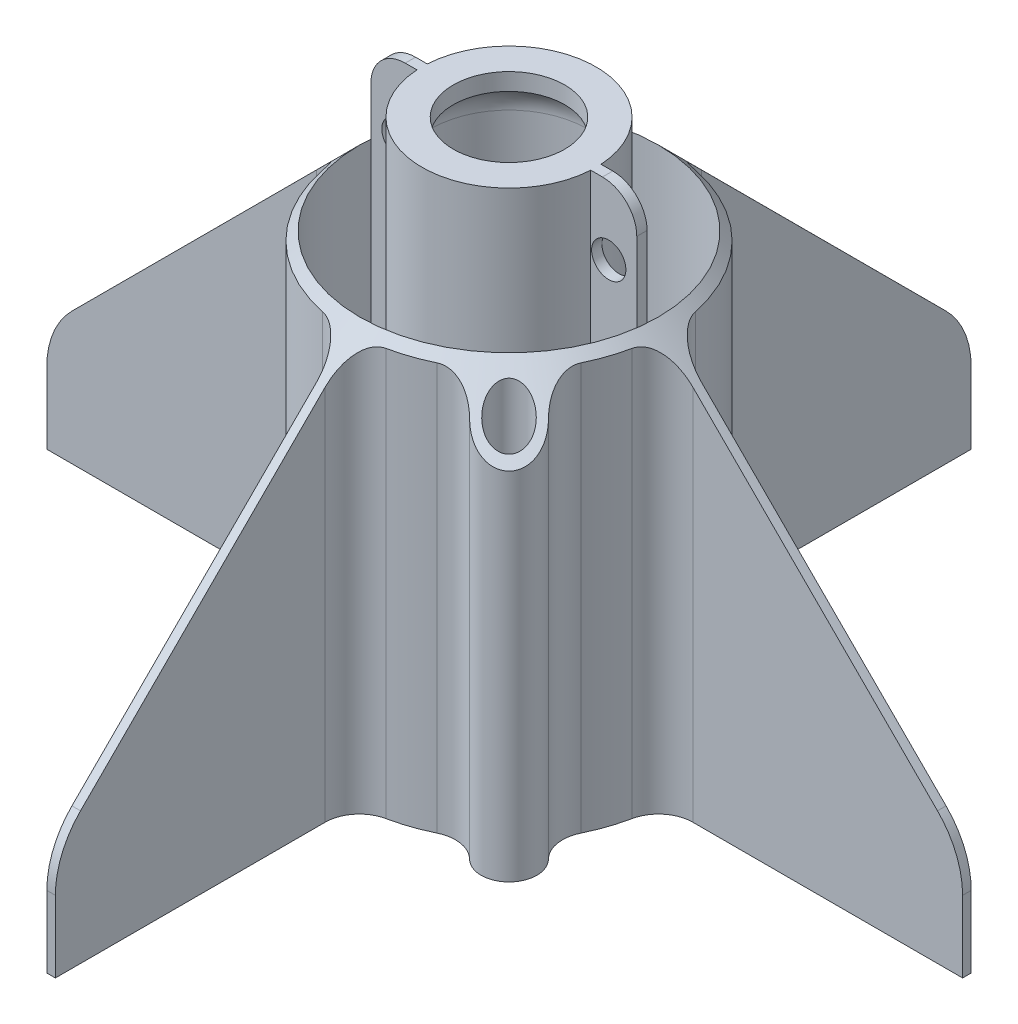
SolidWorks part; units mm, degrees
ref_plane "Front Plane" through (0, 0, 0) normal (0, 0, 1) x (1, 0, 0)
ref_plane "Top Plane" through (0, 0, 0) normal (0, 1, 0) x (1, 0, 0)
ref_plane "Right Plane" through (0, 0, 0) normal (1, 0, 0) x (0, 0, -1)
sketch "Sketch1" plane through (0, 0, 0) normal (0, 0, 1) x (1, 0, 0)
  line L0 (6.5, 60) -> (10.15, 60)
  line L1 (10.15, 60) -> (10.15, 1.5)
  line L2 (10.15, 1.5) -> (17.4, 1.5)
  line L3 (17.4, 1.5) -> (17.4, 50)
  line L4 (17.4, 50) -> (18.4, 50)
  line L5 (18.4, 50) -> (18.4, 0)
  line L6 (18.4, 0) -> (9.15, 0)
  line L7 (9.15, 0) -> (9.15, 58)
  line L8 (9.15, 58) -> (6.5, 58)
  line L9 (6.5, 58) -> (6.5, 60)
  line L10 (0, -33) -> (0, 33) construction
  line L11 (-6.5, 58) -> (-6.5, 60) construction
  line L12 (-9.15, 58) -> (-6.5, 58) construction
  line L13 (-9.15, 0) -> (-9.15, 58) construction
  line L14 (-18.4, 0) -> (-9.15, 0) construction
  line L15 (-18.4, 50) -> (-18.4, 0) construction
  line L16 (-17.4, 50) -> (-18.4, 50) construction
  line L17 (-17.4, 1.5) -> (-17.4, 50) construction
  line L18 (-10.15, 1.5) -> (-17.4, 1.5) construction
  line L19 (-10.15, 60) -> (-10.15, 1.5) construction
  line L20 (-6.5, 60) -> (-10.15, 60) construction
  line L21 (0, 0) -> (0, 125) construction
  dimension "D1" = 2
  dimension "D2" = 1.5
  dimension "D3" = 50
  dimension "D4" = 60
  dimension "D5" = 18.3
  dimension "D6" = 20.3
  dimension "D7" = 13
  dimension "D8" = 34.8
  dimension "D9" = 36.8
revolve "Revolve2" add sketch "Sketch1" angle 360 about L21
sketch "Sketch3" plane through (0, 0, 0) normal (1, 0, 0) x (0, 0, -1)
  line L0 (-18.4, 50) -> (-18.4, 0) construction
  line L1 (-17.9, 50) -> (-17.9, 0) construction
  line L2 (17.4, 50) -> (-17.4, 50) construction
  line L3 (-18.4, 50) -> (-53.4, 50)
  line L4 (18.4, 50) -> (-18.4, 50) construction
  line L5 (-53.4, 50) -> (-53.4, 0)
  line L6 (-53.4, 0) -> (-17.9, 0)
  line L7 (-18.4, 50) -> (-17.9, 50)
  line L8 (-17.9, 50) -> (-17.9, 0)
  dimension "D1" = 0.5
  dimension "D3" = 35
extrude "Boss-Extrude1" add sketch "Sketch3" along normal mid plane 1
pattern_circular "CirPattern1" count 4 over 360 about axis through (0, 0, 0) along (0, -1, 0) of "Boss-Extrude1"
sketch "Sketch7" plane through (0, 0, 0) normal (0, 1, 0) x (1, 0, 0)
  line L0 (0, 0) -> (30.7111, 30.7111) construction
  line L1 (0, 0) -> (72.9642, 0) construction
  dimension "D1" = 45
ref_plane "Plane_direction_guidance" through (0, 0, 0) normal (0.7071, 0, 0.7071) x (0.7071, 0, -0.7071)
sketch "Sketch8" plane through (0, 0, 0) normal (0, 1, 0) x (1, 0, 0)
  line L0 (0, 0) -> (35.9359, -35.9359) construction
  line L1 (53.4, -0.5) -> (18.3932, -0.5) construction
  line L2 (-4.3372, -30.3587) -> (32.1927, 6.1712) construction
  line L3 (-11.0858, -36.4002) -> (34.9415, 9.627) construction
  line L4 (10.3591, -14.9553) -> (12.6572, -17.2534)
  line L5 (10.3591, -14.9553) -> (14.9553, -10.3591)
  line L6 (17.2534, -12.6572) -> (14.9553, -10.3591)
  line L7 (12.6572, -17.2534) -> (17.2534, -12.6572) construction
  line L8 (9.7085, -17.0202) -> (17.8094, -8.9193) construction
  arc A0 (0.5, -18.3932) -> (18.3932, -0.5) centre (0, 0) ccw construction
  arc A1 (12.6572, -17.2534) -> (17.2534, -12.6572) centre (14.9553, -14.9553) ccw
  circle A2 centre (14.9553, -14.9553) radius 2.25 construction
  point P14 (12.6572, -12.6572)
  dimension "D3" = 180
  dimension "D4" = 6.5
  dimension "D5" = 4.5
  dimension "D1" = 45
  dimension "D2" = 0.5
  dimension "D6" = 0.5
extrude "Boss-Extrude3" add sketch "Sketch8" along normal up to surface (50 mm away)
sketch "Sketch9" plane through (0, 0, 0) normal (0, -1, 0) x (1, 0, 0)
  circle A0 centre (14.9553, 14.9553) radius 2.25
  dimension "D1" = 4.5
extrude "Cut-Extrude3" cut sketch "Sketch9" against normal through all both and the other way through all
mirror "Mirror2" about plane through (0, 0, 0) normal (0.7071, 0, 0.7071) of "Boss-Extrude3", "Cut-Extrude3"
sketch "Sketch10" plane through (0, 0, 0) normal (0, 0, 1) x (1, 0, 0)
  line L0 (16.3932, 98.8616) -> (16.3932, -7.2473) construction
  line L1 (58.4, 98.8616) -> (58.4, -16.5651) construction
  line L2 (53.4, 50) -> (53.4, 0) construction
  line L3 (18.3932, 50) -> (18.3932, 0) construction
  line L4 (16.3932, 55) -> (58.4, 55)
  line L5 (58.4, 55) -> (58.4, 7.4932)
  line L6 (58.4, 7.4932) -> (16.3932, 49.5)
  line L7 (16.3932, 49.5) -> (16.3932, 55)
  line L8 (18.3932, 50) -> (53.4, 50) construction
  line L9 (18.3932, 50) -> (15.1043, 50) construction
  line L10 (0, 60) -> (0, 0) construction
  line L11 (10.15, 60) -> (-10.15, 60) construction
  dimension "D1" = 5
  dimension "D2" = 2
  dimension "D3" = 5
  dimension "D4" = 0.5
  dimension "D5" = 45
revolve "Cut-Revolve1" cut sketch "Sketch10" angle 360 about L10
fillet "Fillet2" radius 4 12 edges at (-0.5, 23.7466, 18.3932) (0.5, 23.7466, 18.3932) (18.3932, 23.7466, 0.5) (0.5, 23.7466, -18.3932) (-18.3932, 23.7466, 0.5) (-18.3932, 23.7466, -0.5) (-0.5, 23.7466, -18.3932) (-10.5081, 23.7466, -15.1043) (18.3932, 23.7466, -0.5) (10.5081, 23.7466, 15.1043) (15.1043, 23.7466, 10.5081) (-15.1043, 23.7466, -10.5081)
fillet "Fillet3" radius 6 1 edges at (0, 1.5, -17.4)
fillet "Fillet4" radius 6 1 edges at (0, 1.5, -10.15)
sketch "Sketch11" plane through (0, 0, 0) normal (0, 0, 1) x (1, 0, 0)
  line L0 (-9.65, 60) -> (-15.5, 60)
  line L1 (10.15, 60) -> (-10.15, 60) construction
  line L2 (-15.5, 60) -> (-15.5, 0)
  line L3 (-18.0249, 0) -> (-3.6964, 0) construction
  line L4 (-9.65, 60) -> (-9.65, 0)
  line L5 (-9.65, 0) -> (-15.5, 0)
  line L6 (-10.15, 60) -> (-10.15, 5.1657) construction
  line L9 (0, -33) -> (0, 33) construction
  line L10 (9.65, 60) -> (9.65, 0)
  line L11 (15.5, 60) -> (15.5, 0)
  line L12 (9.65, 0) -> (15.5, 0)
  line L13 (9.65, 60) -> (15.5, 60)
  dimension "D1" = 0.5
  dimension "D2" = 31
extrude "Boss-Extrude4" add sketch "Sketch11" along normal mid plane 1.2
sketch "Sketch12" plane through (0, 0, -0.6) normal (0, 0, -1) x (-1, 0, 0)
  line L0 (10.1323, 60) -> (15.5, 60) construction
  line L1 (10.1323, 60) -> (10.1323, 5.1657) construction
  line L2 (10.2323, 60) -> (10.2323, 0) construction
  line L3 (0, 33) -> (0, -33) construction
  circle A2 centre (12.2323, 52) radius 2
  circle A3 centre (-12.2323, 52) radius 2
  point P7 (0, 0)
  point P8 (0, 0)
  point P9 (0, 0)
  point P10 (0, 0)
  point P11 (0, 0)
  point P12 (10.934, 60)
  point P13 (10.4638, 60)
  dimension "D1" = 0.1
  dimension "D2" = 4
  dimension "D3" = 8
extrude "Cut-Extrude4" cut sketch "Sketch12" against normal up to surface (1.2 mm away) up to face at (12.5983, 25.9851, 0.6)
fillet "Fillet5" radius 10 4 edges
fillet "Fillet6" radius 4 1 edges at (0, 58, -9.15)
fillet "Fillet7" radius 4 2 edges at (-15.5, 60, 0) (15.5, 60, 0)
